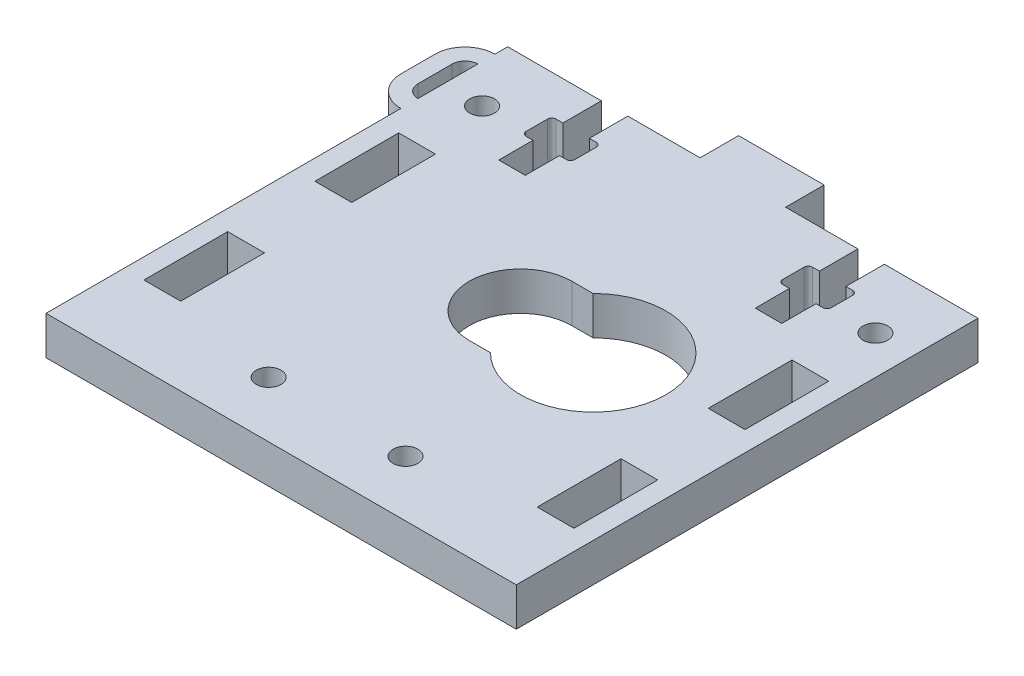
SolidWorks part; units mm, degrees
ref_plane "Front Plane" through (0, 0, 0) normal (0, 0, 1) x (1, 0, 0)
ref_plane "Top Plane" through (0, 0, 0) normal (0, 1, 0) x (1, 0, 0)
ref_plane "Right Plane" through (0, 0, 0) normal (1, 0, 0) x (0, 0, -1)
sketch "Sketch1" plane through (0, 0, 0) normal (0, 1, 0) x (1, 0, 0)
  line L1 (-27.5, 27) -> (27.5, 27)
  line L2 (-27.5, 27) -> (-27.5, -27)
  line L3 (-27.5, -27) -> (27.5, -27)
  line L4 (27.5, 27) -> (27.5, -27)
  line L5 (-27.5, 27) -> (27.5, -27) construction
  line L6 (-27.5, -27) -> (27.5, 27) construction
  point P0 (0, 0)
  dimension "D1" = 55
  dimension "D2" = 54
extrude "MainShape" add sketch "Sketch1" along normal blind 4.5
sketch "Sketch2" plane through (0, 4.5, 0) normal (0, 1, 0) x (1, 0, 0)
  line L0 (0, -27) -> (0, 27) construction
  line L1 (-27.5, -27) -> (27.5, -27) construction
  line L2 (27.5, 27) -> (-27.5, 27) construction
  line L4 (-5, 31.5) -> (5, 31.5)
  line L5 (-5, 31.5) -> (-5, 22.5)
  line L6 (-5, 22.5) -> (5, 22.5)
  line L7 (5, 31.5) -> (5, 22.5)
  line L8 (-5, 31.5) -> (5, 22.5) construction
  line L9 (-5, 22.5) -> (5, 31.5) construction
  dimension "D1" = 10
  dimension "D2" = 4.5
extrude "Tab1" add sketch "Sketch2" against normal through all
sketch "Sketch4" plane through (0, 4.5, 0) normal (0, 1, 0) x (1, 0, 0)
  line L0 (0, 31.5) -> (0, -27) construction
  line L1 (5, 31.5) -> (-5, 31.5) construction
  line L2 (-27.5, -27) -> (27.5, -27) construction
  line L3 (-15, 27) -> (-15, 15) construction
  line L4 (-5, 27) -> (-27.5, 27) construction
  line L5 (-13.45, 15) -> (-16.55, 15) construction
  line L6 (-16.55, 15) -> (-16.55, 27) construction
  line L7 (-13.45, 15) -> (-16.55, 15)
  line L8 (-16.55, 15) -> (-16.55, 19)
  line L9 (-16.55, 19) -> (-17.35, 19)
  line L10 (-17.85, 19.5) -> (-17.85, 22)
  line L11 (-17.35, 22.5) -> (-16.55, 22.5)
  line L12 (-16.55, 22.5) -> (-16.55, 27)
  line L13 (-16.55, 27) -> (-13.45, 27)
  line L14 (-13.45, 15) -> (-13.45, 27) construction
  line L15 (-13.45, 22.5) -> (-13.45, 27)
  line L16 (-12.65, 22.5) -> (-13.45, 22.5)
  line L17 (-12.15, 19.5) -> (-12.15, 22)
  line L18 (-13.45, 19) -> (-12.65, 19)
  line L19 (-13.45, 15) -> (-13.45, 19)
  line L20 (13.45, 15) -> (13.45, 27) construction
  line L21 (16.55, 15) -> (16.55, 27) construction
  line L22 (13.45, 15) -> (16.55, 15) construction
  line L23 (15, 27) -> (15, 15) construction
  line L24 (13.45, 15) -> (13.45, 19)
  line L25 (13.45, 19) -> (12.65, 19)
  line L26 (12.15, 19.5) -> (12.15, 22)
  line L27 (12.65, 22.5) -> (13.45, 22.5)
  line L28 (13.45, 22.5) -> (13.45, 27)
  line L29 (16.55, 27) -> (13.45, 27)
  line L30 (16.55, 22.5) -> (16.55, 27)
  line L31 (17.35, 22.5) -> (16.55, 22.5)
  line L32 (17.85, 19.5) -> (17.85, 22)
  line L33 (16.55, 19) -> (17.35, 19)
  line L34 (16.55, 15) -> (16.55, 19)
  line L35 (13.45, 15) -> (16.55, 15)
  arc A0 (-17.35, 19) -> (-17.85, 19.5) centre (-17.35, 19.5) cw
  arc A1 (-12.15, 19.5) -> (-12.65, 19) centre (-12.65, 19.5) cw
  arc A2 (-12.65, 22.5) -> (-12.15, 22) centre (-12.65, 22) cw
  arc A3 (-17.85, 22) -> (-17.35, 22.5) centre (-17.35, 22) cw
  arc A4 (17.85, 22) -> (17.35, 22.5) centre (17.35, 22) ccw
  arc A5 (12.65, 22.5) -> (12.15, 22) centre (12.65, 22) ccw
  arc A6 (12.15, 19.5) -> (12.65, 19) centre (12.65, 19.5) ccw
  arc A7 (17.35, 19) -> (17.85, 19.5) centre (17.35, 19.5) ccw
  point P24 (-17.85, 19)
  point P27 (-12.15, 19)
  point P30 (-12.15, 22.5)
  point P33 (-17.85, 22.5)
  point P56 (17.85, 22.5)
  point P57 (12.15, 22.5)
  point P58 (12.15, 19)
  point P59 (17.85, 19)
  dimension "D7" = 0.5
  dimension "D1" = 12
  dimension "D2" = 1.55
  dimension "D3" = 3.5
  dimension "D4" = 2.85
  dimension "D5" = 8
  dimension "D6" = 15
extrude "Cut-Extrude2" cut sketch "Sketch4" against normal through all
sketch "Sketch5" plane through (0, 4.5, 0) normal (0, 1, 0) x (1, 0, 0)
  line L0 (0, -27) -> (0, 31.5) construction
  line L1 (-27.5, -27) -> (27.5, -27) construction
  line L2 (5, 31.5) -> (-5, 31.5) construction
  line L3 (23, 27) -> (23, -27) construction
  line L4 (27.5, 27) -> (16.55, 27) construction
  line L5 (-23, 27) -> (-23, -27) construction
  line L6 (20.85, 11.9) -> (25.15, 11.9)
  line L7 (20.85, 11.9) -> (20.85, 2.1)
  line L8 (20.85, 2.1) -> (25.15, 2.1)
  line L9 (25.15, 11.9) -> (25.15, 2.1)
  line L10 (20.85, 11.9) -> (25.15, 2.1) construction
  line L11 (20.85, 2.1) -> (25.15, 11.9) construction
  line L12 (-20.85, 2.1) -> (-25.15, 11.9) construction
  line L13 (-20.85, 11.9) -> (-25.15, 2.1) construction
  line L14 (-25.15, 11.9) -> (-25.15, 2.1)
  line L15 (-20.85, 2.1) -> (-25.15, 2.1)
  line L16 (-20.85, 11.9) -> (-20.85, 2.1)
  line L17 (-20.85, 11.9) -> (-25.15, 11.9)
  line L18 (-27.5, -3) -> (27.5, -3) construction
  line L19 (-27.5, 27) -> (-27.5, -27) construction
  line L20 (27.5, -27) -> (27.5, 27) construction
  line L21 (-20.85, -17.9) -> (-25.15, -8.1) construction
  line L22 (-20.85, -8.1) -> (-25.15, -17.9) construction
  line L23 (20.85, -8.1) -> (25.15, -17.9) construction
  line L24 (20.85, -17.9) -> (25.15, -8.1) construction
  line L25 (-20.85, -17.9) -> (-25.15, -17.9)
  line L26 (-20.85, -17.9) -> (-20.85, -8.1)
  line L27 (-20.85, -8.1) -> (-25.15, -8.1)
  line L28 (-25.15, -17.9) -> (-25.15, -8.1)
  line L29 (25.15, -17.9) -> (25.15, -8.1)
  line L30 (20.85, -8.1) -> (25.15, -8.1)
  line L31 (20.85, -17.9) -> (20.85, -8.1)
  line L32 (20.85, -17.9) -> (25.15, -17.9)
  line L33 (-20.85, 11.9) -> (-25.15, 2.1) construction
  point P10 (23, 7)
  point P21 (-23, 7)
  point P36 (-23, -13)
  point P37 (23, -13)
  dimension "D1" = 23
  dimension "D2" = 9.8
  dimension "D3" = 4.3
  dimension "D4" = 20
  dimension "D5" = 20
extrude "Cut-Extrude3" cut sketch "Sketch5" against normal through all
sketch "Sketch6" plane through (0, 4.5, 0) normal (0, 1, 0) x (1, 0, 0)
  line L0 (0, -27) -> (0, 27) construction
  line L1 (5, 31.5) -> (-5, 31.5) construction
  line L3 (-27.5, 1) -> (27.5, 1) construction
  line L4 (-27.5, 27) -> (-27.5, -27) construction
  line L5 (27.5, -27) -> (27.5, 27) construction
  line L6 (27.5, 27) -> (16.55, 27) construction
  line L7 (-27.5, -27) -> (27.5, -27) construction
  line L9 (-27.5, 27) -> (27.5, 27) construction
  circle A0 centre (0, 1) radius 12
  point P4 (0, 31.5)
  dimension "D1" = 24
  dimension "D2" = 26
extrude "Cut-Extrude4" cut sketch "Sketch6" against normal through all
sketch "Sketch7" plane through (0, 4.5, 0) normal (0, 1, 0) x (1, 0, 0)
  line L0 (0, 1) -> (0, -27) construction
  line L3 (-27.5, -27) -> (27.5, -27) construction
  line L4 (8, -20.46) -> (-8, -20.46) construction
  circle A1 centre (-8, -20.46) radius 1.45
  circle A2 centre (8, -20.46) radius 1.45
  point P8 (0, -20.46)
  dimension "D1" = 2.9
  dimension "D3" = 21.46
extrude "Cut-Extrude5" [suppressed] cut sketch "Sketch7" against normal through all
sketch "Sketch8" plane through (0, 4.5, 0) normal (0, 1, 0) x (1, 0, 0)
  line L0 (-12, 1) -> (12, 1) construction
  line L1 (0, 1) -> (0, -20.46) construction
  line L2 (8, -20.46) -> (-8, -20.46) construction
  line L3 (0, -11) -> (0, 13) construction
  circle A0 centre (-8, -20.46) radius 1.45
  circle A1 centre (0, 1) radius 12 construction
  circle A2 centre (8, -20.46) radius 1.45
  dimension "D3" = 2.9
  dimension "D1" = 90
  dimension "D4" = 21.46
extrude "Cut-Extrude6" cut sketch "Sketch8" against normal through all
sketch "Sketch9" plane through (0, 4.5, 0) normal (0, 1, 0) x (1, 0, 0)
  line L0 (0, -27) -> (0, 31.5) construction
  line L1 (-27.5, -27) -> (27.5, -27) construction
  line L2 (5, 31.5) -> (-5, 31.5) construction
  line L3 (16, -27) -> (16, -16) construction
  line L4 (14.45, -16) -> (17.55, -16) construction
  line L5 (17.55, -16) -> (17.55, -27) construction
  line L6 (17.55, -27) -> (17.55, -22.5)
  line L7 (17.55, -22.5) -> (18.35, -22.5)
  line L8 (18.85, -22) -> (18.85, -19.5)
  line L9 (18.35, -19) -> (17.55, -19)
  line L10 (17.55, -19) -> (17.55, -16)
  line L11 (17.55, -16) -> (14.45, -16)
  line L12 (17.55, -27) -> (14.45, -27)
  line L13 (14.45, -16) -> (14.45, -27) construction
  line L14 (14.45, -19) -> (14.45, -16)
  line L15 (13.65, -19) -> (14.45, -19)
  line L16 (13.15, -22) -> (13.15, -19.5)
  line L17 (14.45, -22.5) -> (13.65, -22.5)
  line L18 (14.45, -27) -> (14.45, -22.5)
  line L19 (-14.45, -16) -> (-14.45, -27) construction
  line L20 (-17.55, -16) -> (-17.55, -27) construction
  line L21 (-14.45, -16) -> (-17.55, -16) construction
  line L22 (-16, -27) -> (-16, -16) construction
  line L23 (-14.45, -27) -> (-14.45, -22.5)
  line L24 (-14.45, -22.5) -> (-13.65, -22.5)
  line L25 (-13.15, -22) -> (-13.15, -19.5)
  line L26 (-13.65, -19) -> (-14.45, -19)
  line L27 (-14.45, -19) -> (-14.45, -16)
  line L28 (-17.55, -27) -> (-14.45, -27)
  line L29 (-17.55, -16) -> (-14.45, -16)
  line L30 (-17.55, -19) -> (-17.55, -16)
  line L31 (-18.35, -19) -> (-17.55, -19)
  line L32 (-18.85, -22) -> (-18.85, -19.5)
  line L33 (-17.55, -22.5) -> (-18.35, -22.5)
  line L34 (-17.55, -27) -> (-17.55, -22.5)
  arc A0 (18.35, -22.5) -> (18.85, -22) centre (18.35, -22) ccw
  arc A1 (18.85, -19.5) -> (18.35, -19) centre (18.35, -19.5) ccw
  arc A2 (13.15, -19.5) -> (13.65, -19) centre (13.65, -19.5) cw
  arc A3 (13.65, -22.5) -> (13.15, -22) centre (13.65, -22) cw
  arc A4 (-13.65, -22.5) -> (-13.15, -22) centre (-13.65, -22) ccw
  arc A5 (-13.15, -19.5) -> (-13.65, -19) centre (-13.65, -19.5) ccw
  arc A6 (-18.85, -19.5) -> (-18.35, -19) centre (-18.35, -19.5) cw
  arc A7 (-18.35, -22.5) -> (-18.85, -22) centre (-18.35, -22) cw
  point P16 (18.85, -22.5)
  point P19 (18.85, -19)
  point P30 (13.15, -19)
  point P31 (13.15, -22.5)
  point P54 (-13.15, -22.5)
  point P55 (-13.15, -19)
  point P56 (-18.85, -19)
  point P57 (-18.85, -22.5)
  dimension "D7" = 0.5
  dimension "D2" = 1.55
  dimension "D1" = 11
  dimension "D3" = 8
  dimension "D4" = 3.5
  dimension "D5" = 2.85
  dimension "D6" = 16
extrude "Cut-Extrude7" [suppressed] cut sketch "Sketch9" against normal through all
sketch "Sketch10" [suppressed] plane through (0, 0, 27) normal (0, 0, 1) x (1, 0, 0)
  line L0 (-27.5, 2.25) -> (27.5, 2.25) construction
  line L1 (-27.5, 4.5) -> (-27.5, 0) construction
  line L2 (27.5, 4.5) -> (27.5, 0) construction
  line L3 (-16, 4.5) -> (-16, 0) construction
  line L4 (-14.25, 4.5) -> (-17.75, 4.5) construction
  line L5 (16, 4.5) -> (16, 0) construction
  line L6 (17.75, 4.5) -> (14.25, 4.5) construction
  line L7 (17.75, 0) -> (14.25, 0) construction
  line L8 (-14.25, 0) -> (-17.75, 0) construction
  circle A0 centre (-16, 2.25) radius 1.6
  circle A1 centre (16, 2.25) radius 1.6
  dimension "D1" = 3.2
  dimension "D2" = 3.2
sketch "Sketch11" plane through (0, 4.5, 0) normal (0, 1, 0) x (1, 0, 0)
  line L0 (-20.85, 7) -> (-25.15, 7) construction
  line L1 (-20.85, 2.1) -> (-20.85, 11.9) construction
  line L2 (-25.15, 11.9) -> (-25.15, 2.1) construction
  line L3 (-23, 7) -> (-23, 27) construction
  line L4 (-16.55, 27) -> (-27.5, 27) construction
  line L5 (0, 31.5) -> (0, 0) construction
  line L6 (5, 31.5) -> (-5, 31.5) construction
  line L7 (23, 7) -> (23, 27) construction
  line L8 (20.85, 7) -> (25.15, 7) construction
  line L9 (-23, 7) -> (-23, 27) construction
  circle A0 centre (-23, 19.5) radius 1.45
  circle A1 centre (23, 19.5) radius 1.45
  dimension "D1" = 2.9
  dimension "D2" = 7.5
extrude "Cut-Extrude8" cut sketch "Sketch11" against normal through all
sketch "Sketch12" [suppressed] plane through (0, 4.5, 0) normal (0, 1, 0) x (1, 0, 0)
  line L0 (-27.5, -7) -> (-34, -17)
  line L1 (-27.5, 27) -> (-27.5, -27) construction
  line L2 (-34, -17) -> (-34, -27)
  line L3 (-34, -27) -> (-27.5, -27)
  line L4 (-27.5, -27) -> (-27.5, -7)
  line L5 (-27.5, -27) -> (27.5, -27) construction
  line L6 (0, -27) -> (0, 31.5) construction
  line L7 (5, 31.5) -> (-5, 31.5) construction
  line L8 (27.5, -27) -> (27.5, -7)
  line L9 (34, -27) -> (27.5, -27)
  line L10 (34, -17) -> (34, -27)
  line L11 (27.5, -7) -> (34, -17)
  point P4 (0, -27)
  dimension "D1" = 34
  dimension "D2" = 10
  dimension "D3" = 20
extrude "Boss-Extrude1" [suppressed] add sketch "Sketch12" against normal through all
sketch "Sketch14" [suppressed] plane through (0, 4.5, 0) normal (0, 1, 0) x (1, 0, 0)
  line L0 (-34, -27) -> (34, -27) construction
  line L2 (-34, -27) -> (34, -27) construction
  line L3 (0, -27) -> (0, 31.5) construction
  line L4 (5, 31.5) -> (-5, 31.5) construction
  line L6 (26.25, -16.5) -> (26.25, -27) construction
  line L8 (-28, -27) -> (-28, -16.5) construction
  line L9 (-26.25, -16.5) -> (-29.75, -16.5) construction
  line L10 (-29.75, -16.5) -> (-29.75, -27) construction
  line L11 (-26.25, -27) -> (-29.75, -27)
  line L12 (-29.75, -27) -> (-29.75, -23.2)
  line L13 (-29.75, -23.2) -> (-30.75, -23.2)
  line L14 (-31, -22.95) -> (-31, -19.25)
  line L15 (-30.75, -19) -> (-29.75, -19)
  line L16 (-29.75, -19) -> (-29.75, -16.5)
  line L17 (-29.75, -16.5) -> (-26.25, -16.5)
  line L18 (-26.25, -16.5) -> (-26.25, -27) construction
  line L19 (-26.25, -19) -> (-26.25, -16.5)
  line L20 (-25.25, -19) -> (-26.25, -19)
  line L21 (-25, -22.95) -> (-25, -19.25)
  line L22 (-26.25, -23.2) -> (-25.25, -23.2)
  line L23 (-26.25, -27) -> (-26.25, -23.2)
  line L24 (29.75, -16.5) -> (29.75, -27) construction
  line L25 (26.25, -16.5) -> (29.75, -16.5) construction
  line L26 (28, -27) -> (28, -16.5) construction
  line L27 (26.25, -27) -> (26.25, -23.2)
  line L28 (26.25, -23.2) -> (25.25, -23.2)
  line L29 (25, -22.95) -> (25, -19.25)
  line L30 (25.25, -19) -> (26.25, -19)
  line L31 (26.25, -19) -> (26.25, -16.5)
  line L32 (29.75, -16.5) -> (26.25, -16.5)
  line L33 (29.75, -19) -> (29.75, -16.5)
  line L34 (30.75, -19) -> (29.75, -19)
  line L35 (31, -22.95) -> (31, -19.25)
  line L36 (29.75, -23.2) -> (30.75, -23.2)
  line L37 (29.75, -27) -> (29.75, -23.2)
  line L38 (26.25, -27) -> (29.75, -27)
  line L39 (-26.25, -16.5) -> (-26.25, -27) construction
  arc A0 (-30.75, -23.2) -> (-31, -22.95) centre (-30.75, -22.95) cw
  arc A1 (-31, -19.25) -> (-30.75, -19) centre (-30.75, -19.25) cw
  arc A2 (-25, -19.25) -> (-25.25, -19) centre (-25.25, -19.25) ccw
  arc A3 (-25.25, -23.2) -> (-25, -22.95) centre (-25.25, -22.95) ccw
  arc A4 (25.25, -23.2) -> (25, -22.95) centre (25.25, -22.95) cw
  arc A5 (25, -19.25) -> (25.25, -19) centre (25.25, -19.25) cw
  arc A6 (31, -19.25) -> (30.75, -19) centre (30.75, -19.25) ccw
  arc A7 (30.75, -23.2) -> (31, -22.95) centre (30.75, -22.95) ccw
  point P2 (0, -27)
  dimension "D10" = 0.5
  dimension "D4" = 1.55
  dimension "D6" = 11
  dimension "D2" = 28
  dimension "D3" = 2.85
  dimension "D5" = 3.5
  dimension "D7" = 8
extrude "Cut-Extrude9" [suppressed] cut sketch "Sketch14" against normal through all
sketch "Sketch15" plane through (0, 4.5, 0) normal (0, 1, 0) x (1, 0, 0)
  circle A0 centre (0, 1) radius 12
  circle A1 centre (0, 1) radius 6
  circle A2 centre (0, 1) radius 12 construction
  dimension "D1" = 12
extrude "Boss-Extrude2" add sketch "Sketch15" against normal through all
sketch "Sketch16" plane through (0, 4.5, 0) normal (0, 1, 0) x (1, 0, 0)
  line L0 (0, 1) -> (27.5, 1) construction
  line L1 (27.5, -27) -> (27.5, 27) construction
  line L2 (0, 7) -> (2.4792, 7)
  line L3 (0, -5) -> (2.4792, -5)
  line L4 (0, 7) -> (0, -5)
  arc A0 (2.4792, -5) -> (2.4792, 7) centre (8.5, 1) ccw
  circle A1 centre (0, 1) radius 6 construction
  dimension "D1" = 17
  dimension "D2" = 8.5
extrude "Cut-Extrude10" cut sketch "Sketch16" against normal through all
sketch "Sketch17" plane through (0, 4.5, 0) normal (0, 1, 0) x (1, 0, 0)
  line L0 (-27.5, 22) -> (-27.5, 18) construction
  line L1 (-27.5, 27) -> (-27.5, -27) construction
  line L2 (-27.5, 25.5) -> (-27.5, 23.5)
  line L3 (-29, 22) -> (-29, 18)
  line L4 (-27.5, 22) -> (-27.5, 18) construction
  line L5 (-27.5, 16.5) -> (-27.5, 14.5)
  line L6 (-31, 22) -> (-31, 18)
  line L7 (-27.5, 25.5) -> (-27.5, 14.5) construction
  arc A0 (-27.5, 23.5) -> (-29, 22) centre (-27.5, 22) ccw
  arc A1 (-29, 18) -> (-27.5, 16.5) centre (-27.5, 18) ccw
  arc A2 (-27.5, 25.5) -> (-31, 22) centre (-27.5, 22) ccw
  arc A3 (-31, 18) -> (-27.5, 14.5) centre (-27.5, 18) ccw
  point P10 (-27.5, 20)
  dimension "D1" = 1.5
  dimension "D2" = 1.5
  dimension "D3" = 2
  dimension "D4" = 4
  dimension "D5" = 20
  dimension "D7" = 2
extrude "CableTieSlot" add sketch "Sketch17" against normal through all
equation "\"X-ROD-SPACING\"=45"
equation "\"Y-ROD-SPACING\"=75"
equation "\"Z-ROD-SPACING\"=17.5"
equation "\"Y-BED-OFFSET\"=2"
equation "\"Y-BED-ROD-INSET\"=3.5"
equation "\"Y-BED-SCREW-SPACING\"=209"
equation "\"Y-BED-SCREW-CUTOUT-SLOT-HEIGHT\"=2"
equation "\"T-SLOT-NUT-FILLET-RADIUS\"=0.5"
equation "\"T-SLOT-SCREW-SHAFT-RADIUS\"=1.55"
equation "\"T-SLOT-SCREW-SHAFT-CUTOUT-LENGTH\"=11.0"
equation "\"T-SLOT-NUT-DEPTH\"=3.5"
equation "\"T-SLOT-NUT-WIDTH\"=2.85"
equation "\"T-SLOT-NUT-END-DISTANCE\"=8"
equation "\"ACRYLIC-THICKNESS\"=10"
equation "\"ACRYLIC-THICKNESS2\"=4.5"
equation "\"ACRYLIC-TAB-CUTOUT-SIZE\"=\"ACRYLIC-THICKNESS\"+\"ACRYLIC-TAB-TOLERANCE\"*2"
equation "\"ACRYLIC-TAB-WIDTH\"=\"ACRYLIC-THICKNESS\""
equation "\"ACRYLIC-M3-HOLE\"=2.9"
equation "\"SMOOTHROD-CAP-SCREW-DISTANCE\"=20"
equation "\"FRAME-WIDTH-INNER\"=370"
equation "\"NEMA17-HOLE-SPACING\"=31"
equation "\"NEMA17-CENTRAL-CUTOUT\"=22.5"
equation "\"Z-BRACKET-REACH\"=55"
equation "\"Z-ROD-INSET\"=16"
equation "\"TOP-BRACKET-SPACING\"=40"
equation "\"SMOOTHROD-X-LENGTH\"=350"
equation "\"SMOOTHROD-Y-LENGTH\"=350"
equation "\"SMOOTHROD-Z-LENGTH\"=350"
equation "\"SMOOTHROD-TIGHTENING-HEADROOM\"=.25"
equation "\"LEADSCREW-Z-LENGTH\"=300"
equation "\"SCREW-LENGTH-FRAME\"=\"ACRYLIC-THICKNESS\" + 10"
equation "\"SCREW-LENGTH-MOTOR\"=\"ACRYLIC-THICKNESS\" + 5"
equation "\"SCREW-LENGTH-EXTRUDER\"=28"
equation "\"SCREW-HEAD-RADIUS\"=6"
equation "\"PRINTED-X-SMOOTHROD-DIAMETER\"=9.0"
equation "\"PRINTED-X-SMOOTHROD-CUTOUT\"=10"
equation "\"PRINTED-X-BASE-HEIGHT\"=10"
equation "\"PRINTED-LM8UU-CUTOUT-SIZE\"=15.5"
equation "\"PRINTED-LM8UU-CUTOUT-LENGTH\"=24.5"
equation "\"PRINTED-X-IDLER-HEIGHT\"=16"
equation "\"PSU-MOUNTING-WIDTH\"=95"
equation "\"PSU-MOUNTING-HEIGHT\"=177"
equation "\"Y-BELT-TO-ROD-DISTANCE\"=20"
equation "\"SPOOL-HOLDER-ROD-SPACING\"=150"
equation "\"ACRYLIC-X-CARRIAGE-WIDTH\"=55"
equation "\"ACRYLIC-X-CARRIAGE-HEIGHT\"=75"
equation "\"ACRYLIC-X-CARRIAGE-SCREW-SPACING-X\"=15"
equation "\"ACRYLIC-X-CARRIAGE-SCREW-SPACING-Y\"=33"
equation "\"ACRYLIC-X-CARRIAGE-CENTER-TAB-SPACING\"=14"
equation "\"D1@Sketch1\"=\"ACRYLIC-X-CARRIAGE-WIDTH\""
equation "\"D1@MainShape\" = \"ACRYLIC-THICKNESS2\""
equation "\"D1@Sketch2\"=\"ACRYLIC-TAB-WIDTH\""
equation "\"D2@Sketch2\"=\"ACRYLIC-THICKNESS2\""
equation "\"D1@Sketch4\"=\"T-SLOT-SCREW-SHAFT-CUTOUT-LENGTH\"+1"
equation "\"D2@Sketch4\"=\"T-SLOT-SCREW-SHAFT-RADIUS\""
equation "\"D3@Sketch4\"=\"T-SLOT-NUT-DEPTH\""
equation "\"D4@Sketch4\"=\"T-SLOT-NUT-WIDTH\""
equation "\"D5@Sketch4\"=\"T-SLOT-NUT-END-DISTANCE\""
equation "\"D6@Sketch4\"=\"ACRYLIC-X-CARRIAGE-SCREW-SPACING-X\""
equation "\"D7@Sketch4\"=\"T-SLOT-NUT-FILLET-RADIUS\""
equation "\"ACRYLIC-X-CARRIAGE-EXTRUDER-SHELF-DEPTH\"=\"ACRYLIC-X-CARRIAGE-EXTRUDER-OFFSET\" + 28"
equation "\"D2@Sketch1\"=\"ACRYLIC-X-CARRIAGE-EXTRUDER-SHELF-DEPTH\""
equation "\"ACRYLIC-X-CARRIAGE-LM8UU-CUTOUT-WIDTH\"=24.25"
equation "\"ACRYLIC-X-CARRIAGE-EXTRUDER-BRACE-SPACING\"=23"
equation "\"ACRYLIC-X-CARRIAGE-EXTRUDER-BRACE-TAB-OFFSET\"=20"
equation "\"ACRYLIC-X-CARRIAGE-EXTRUDER-BRACE-HEIGHT\"=35"
equation "\"ACRYLIC-X-CARRIAGE-EXTRUDER-BRACE-SCREW-SPACING\"=22"
equation "\"D1@Sketch5\"=\"ACRYLIC-X-CARRIAGE-EXTRUDER-BRACE-SPACING\""
equation "\"D2@Sketch5\"=\"ACRYLIC-TAB-WIDTH\"-\"KERF\"*2"
equation "\"D3@Sketch5\"=\"ACRYLIC-THICKNESS2\"-\"KERF\"*2"
equation "\"D4@Sketch5\"=\"ACRYLIC-X-CARRIAGE-EXTRUDER-BRACE-TAB-OFFSET\""
equation "\"D1@Sketch7\"=\"ACRYLIC-M3-HOLE\""
equation "\"D3@Sketch8\"=\"ACRYLIC-M3-HOLE\""
equation "\"ACRYLIC-X-CARRIAGE-EXTRUDER-ANGLE\"=90"
equation "\"D1@Sketch8\"=\"ACRYLIC-X-CARRIAGE-EXTRUDER-ANGLE\""
equation "\"ACRYLIC-X-CARRIAGE-EXTRUDER-OFFSET\"=26"
equation "\"D2@Sketch6\"=\"ACRYLIC-X-CARRIAGE-EXTRUDER-OFFSET\""
equation "\"D1@Sketch9\"=\"T-SLOT-SCREW-SHAFT-CUTOUT-LENGTH\""
equation "\"D2@Sketch9\"=\"T-SLOT-SCREW-SHAFT-RADIUS\""
equation "\"D3@Sketch9\"=\"T-SLOT-NUT-END-DISTANCE\""
equation "\"D4@Sketch9\"=\"T-SLOT-NUT-DEPTH\""
equation "\"D5@Sketch9\"=\"T-SLOT-NUT-WIDTH\""
equation "\"D7@Sketch9\"=\"T-SLOT-NUT-FILLET-RADIUS\""
equation "\"ACRYLIC-TAB-TOLERANCE\"=-.05"
equation "\"D1@Sketch11\"=\"ACRYLIC-M3-HOLE\""
equation "\"D6@Sketch14\"=\"T-SLOT-SCREW-SHAFT-CUTOUT-LENGTH\""
equation "\"D3@Sketch14\"=\"T-SLOT-NUT-WIDTH\""
equation "\"D5@Sketch14\"=\"T-SLOT-NUT-DEPTH\""
equation "\"D4@Sketch14\"=\"T-SLOT-SCREW-SHAFT-RADIUS\""
equation "\"D10@Sketch14\"=\"T-SLOT-NUT-FILLET-RADIUS\""
equation "\"D7@Sketch14\"=\"T-SLOT-NUT-END-DISTANCE\""
equation "\"KERF\"=0.1"
equation "\"PRINTED-M3-HOLE\"=3.5"
equation "\"PRINTED-M3-NUT-AF\"=6.25"
equation "\"ACRYLIC-X-CARRIAGE-LM8UU-CUTOUT-HEIGHT\"=11.0"
equation "\"ACRYLIC-X-CARRIAGE-DUAL-WIDTH-MULTIPLIER\"=1.65"
equation "\"ACRYLIC-X-CARRIAGE-DUAL-HOTEND-SPACING\"=42"
equation "\"ACRYLIC-X-CARRIAGE-DUAL-WIDTH\"=75"
equation "\"ACRYLIC-X-CARRIAGE-DUAL-FAN-OFFSET\"=52"
equation "\"ACRYLIC-X-CARRIAGE-DUAL-FAN-HEIGHT\"=20"
equation "\"ACRYLIC-X-CARRIAGE-DUAL-HOTEND-SEPARATION\"=36"
equation "\"ACRYLIC-X-CARRIAGE-DUAL-MOUNT-PLATE-DEPTH\"=75"
equation "\"ACRYLIC-X-CARRIAGE-DUAL-MOUNT-BRACE-WIDTH\"=33"
equation "\"ACRYLIC-X-CARRIAGE-DUAL-MOUNT-SCREW-WIDTH\"=40"
equation "\"BLOWER-FAN-WIDTH\"=15"
